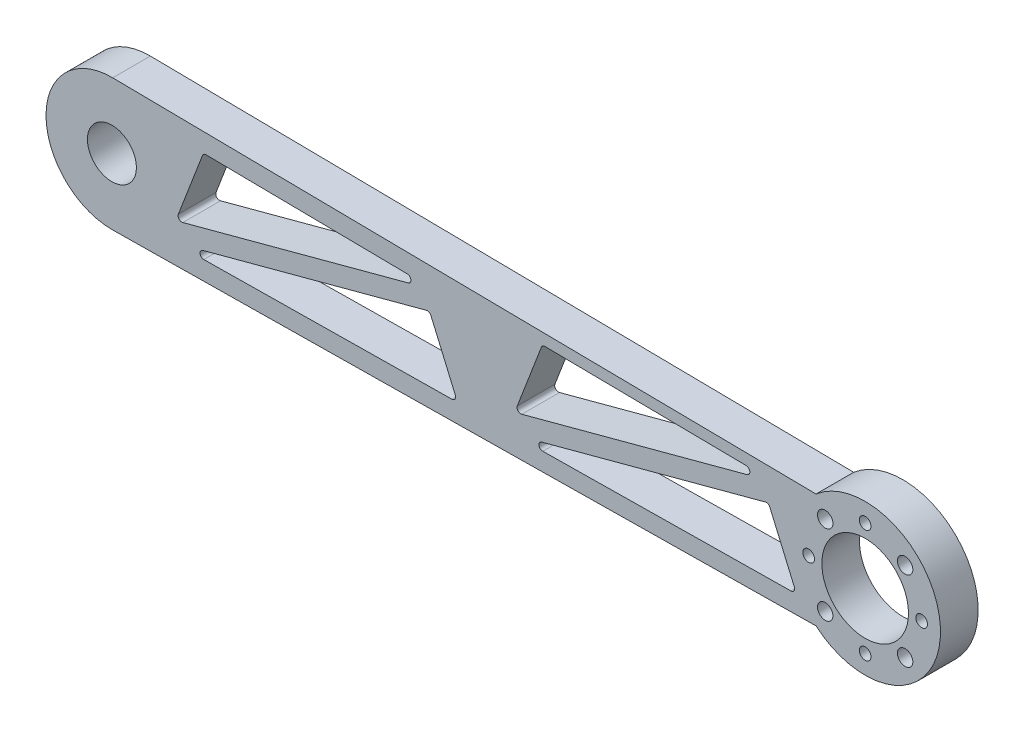
SolidWorks part; units mm, degrees
ref_plane "前视基准面" through (0, 0, 0) normal (0, 0, 1) x (1, 0, 0)
ref_plane "上视基准面" through (0, 0, 0) normal (0, 1, 0) x (1, 0, 0)
ref_plane "右视基准面" through (0, 0, 0) normal (1, 0, 0) x (0, 0, -1)
sketch "草图1" plane through (0, 0, 0) normal (0, 0, 1) x (1, 0, 0)
  line L0 (0.2188, 17.4986) -> (200.1875, 14.9988)
  line L1 (0, 0) -> (200, 0) construction
  line L2 (0.2188, -17.4986) -> (200.1875, -14.9988)
  circle A0 centre (0, 0) radius 17.5
  circle A1 centre (200, 0) radius 15
  dimension "D1" = 35
  dimension "20" = 30
  dimension "D3" = 200
extrude "凸台-拉伸1" add sketch "草图1" along normal blind 10 contours A0 | A0 L1 A1 L0 | L1 A0 L2 A1 | A1 region at (99.0773, 8.3131, 0) region at (12.0993, 11.949, 0) region at (210.3708, 10.242, 0) region at (99.0773, -8.3131, 0)
sketch "草图2" plane through (0, 0, 10) normal (0, 0, 1) x (1, 0, 0)
  circle A0 centre (0, 0) radius 6.5
  dimension "D1" = 13
extrude "切除-拉伸1" cut sketch "草图2" against normal blind 10
sketch "草图3" plane through (0, 0, 10) normal (0, 0, 1) x (1, 0, 0)
  line L0 (24.289, 12.1973) -> (85.6581, 11.4302)
  line L1 (85.6581, 11.4302) -> (16.9374, -6.9794)
  line L2 (16.9374, -6.9794) -> (24.289, 12.1973)
  line L3 (16.4146, -12.2958) -> (84.3461, 5.9024)
  line L4 (84.3461, 5.9024) -> (91.7811, -11.3536)
  line L5 (91.7811, -11.3536) -> (16.4146, -12.2958)
  line L6 (0.2188, -17.4986) -> (200.1875, -14.9988) construction
  line L7 (0.2188, 17.4986) -> (200.1875, 14.9988) construction
  line L8 (100.2031, 16.2487) -> (100.2031, -16.2487) construction
  line L9 (106.9328, -6.0644) -> (114.2844, 13.1124)
  line L10 (114.2844, 13.1124) -> (175.6535, 12.3452)
  line L11 (175.6535, 12.3452) -> (106.9328, -6.0644)
  line L12 (181.7765, -10.4386) -> (106.41, -11.3808)
  line L13 (106.41, -11.3808) -> (174.3414, 6.8174)
  line L14 (174.3414, 6.8174) -> (181.7765, -10.4386)
  dimension "D1" = 5
  dimension "D2" = 5
  dimension "D3" = 5
  dimension "D4" = 2
extrude "切除-拉伸2" cut sketch "草图3" against normal blind 10 contours L2 L0 L1 | L5 L3 L4 | L9 L10 L11 | L12 L13 L14
fillet "圆角1" radius 1 12 edges at (174.3414, 6.8174, 5) (181.7765, -10.4386, 5) (175.6535, 12.3452, 5) (106.41, -11.3808, 5) (106.9328, -6.0644, 5) (114.2844, 13.1124, 5) (84.3461, 5.9024, 5) (91.7811, -11.3536, 5) (16.4146, -12.2958, 5) (24.289, 12.1973, 5) (85.6581, 11.4302, 5) (16.9374, -6.9794, 5)
sketch "草图4" plane through (0, 0, 10) normal (0, 0, 1) x (1, 0, 0)
  line L0 (0.2188, 17.4986) -> (200.1875, 14.9988) construction
  line L1 (186.9598, 15.1642) -> (200.1875, 14.9988)
  line L2 (0.2188, -17.4986) -> (200.1875, -14.9988) construction
  line L3 (186.9598, -15.1642) -> (200.1875, -14.9988)
  arc A0 (186.9598, -15.1642) -> (186.9598, 15.1642) centre (200, 0) ccw
  arc A1 (200.1875, -14.9988) -> (200.1875, 14.9988) centre (200, 0) ccw construction
  arc A2 (200.1875, -14.9988) -> (200.1875, 14.9988) centre (200, 0) ccw
  dimension "D1" = 40
extrude "凸台-拉伸2" add sketch "草图4" against normal up to surface (10 mm away) contours L1 A0 L3 A2 up to face at (130.4815, 6.4286, 0)
sketch "草图5" plane through (0, 0, 10) normal (0, 0, 1) x (1, 0, 0)
  line L0 (189.3934, 10.6066) -> (200, 0)
  line L1 (200, 0) -> (200, 15) construction
  circle A0 centre (200, 0) radius 15 construction
  circle A1 centre (200, 15) radius 1.55
  circle A2 centre (215, 0) radius 1.55
  circle A3 centre (200, -15) radius 1.55
  circle A4 centre (185, 0) radius 1.55
  circle A5 centre (189.3934, 10.6066) radius 2.05
  circle A6 centre (210.6066, 10.6066) radius 2.05
  circle A7 centre (210.6066, -10.6066) radius 2.05
  circle A8 centre (189.3934, -10.6066) radius 2.05
  point P14 (200, 0)
  point P23 (200, 0)
  dimension "D1" = 30
  dimension "D2" = 3.1
  dimension "D5" = 4.1
  dimension "D4" = 45
  dimension "D3" = 4
  dimension "D6" = 4
extrude "切除-拉伸3" cut sketch "草图5" against normal blind 10 contours A5 | A1 | A6 | A2 | A7 | A3 | A8 | A4 region at (200, 15, 10) region at (215, 0, 10) region at (200, -15, 10) region at (185, 0, 10) region at (191.2338, 9.8443, 10) region at (210.6066, 10.6066, 10) region at (210.6066, -10.6066, 10) region at (189.3934, -10.6066, 10)
sketch "草图6" plane through (0, 0, 10) normal (0, 0, 1) x (1, 0, 0)
  circle A0 centre (200, 0) radius 11.5
  dimension "D1" = 23
extrude "切除-拉伸4" cut sketch "草图6" against normal blind 10
